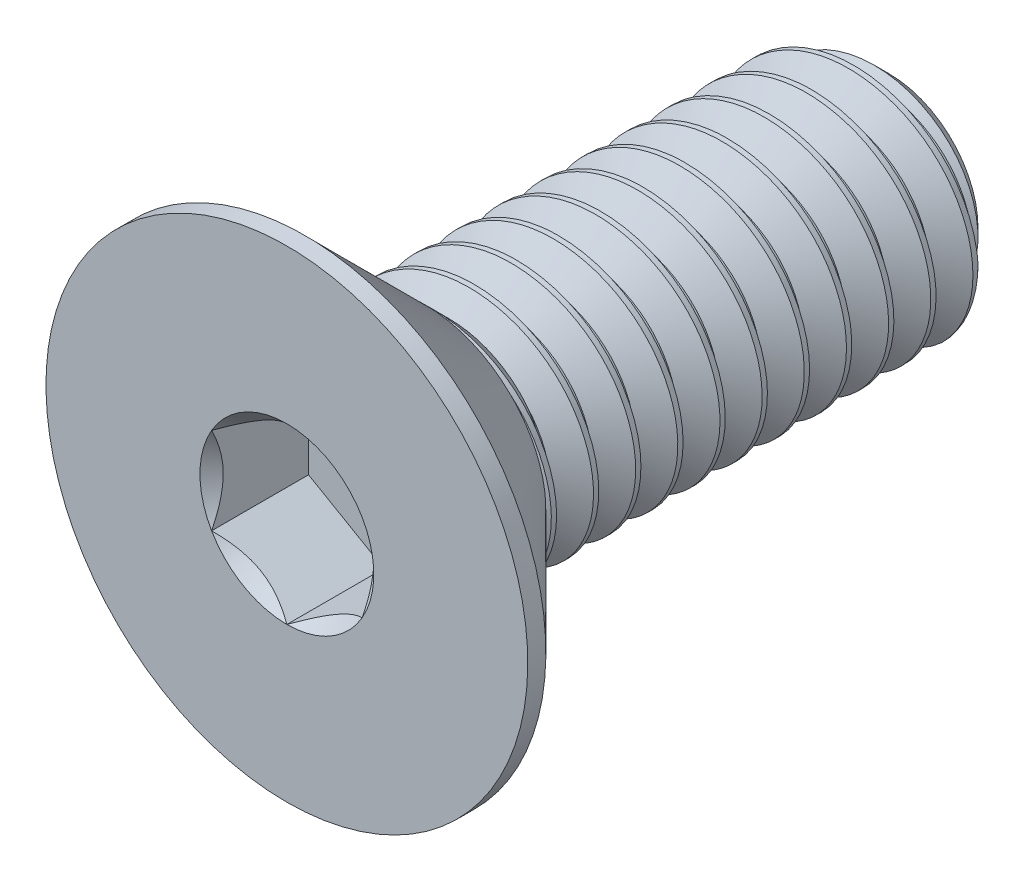
SolidWorks part; units mm, degrees
ref_plane "Front" through (0, 0, 0) normal (0, 0, 1) x (1, 0, 0)
ref_plane "Top" through (0, 0, 0) normal (0, 1, 0) x (1, 0, 0)
ref_plane "Right" through (0, 0, 0) normal (1, 0, 0) x (0, 0, -1)
sketch "Sketch1" plane through (0, 0, 0) normal (1, 0, 0) x (0, 0, -1)
  line L0 (0, 4) -> (0.3, 4) construction
  line L1 (0.3, 4) -> (2.3, 2) construction
  line L2 (0, 2) -> (10, 2)
  line L3 (10, 2) -> (10, 0)
  line L4 (10, 0) -> (0, 0)
  line L5 (0, 0) -> (0, 4) construction
  line L6 (0, 4) -> (0, -4) construction
  line L7 (10, 2) -> (10, -2) construction
  line L8 (0, -4) -> (0.3, -4) construction
  line L9 (0.3, -4) -> (2.3, -2) construction
  line L11 (0, 2) -> (0, 0)
  line L12 (2.3, 2) -> (2.3, 0) construction
  dimension "Head Ht" = 2.3
  dimension "Head Dia" = 8
  dimension "Dia" = 4
  dimension "Lg" = 10
  dimension "Head Angle" = 90
revolve "Revolve1" add sketch "Sketch1" angle 360 mid plane about L4
sketch "Sketch3" plane through (0, 0, -10) normal (0, 0, -1) x (-1, 0, 0)
  circle A0 centre (0, 0) radius 2
curve "Helix/Spiral1" pitch 0.7 height 10 radius 2 centre (0, 0, -10) axis (0, 0, 1) start towards (0, 1, 0)
sketch "Sketch2" plane through (0, 0, 0) normal (1, 0, 0) x (0, 0, -1)
  line L0 (10, 2) -> (10.6125, 2)
  line L1 (10.6125, 2) -> (10.35, 1.5453)
  line L2 (10.35, 1.5453) -> (10.2625, 1.5453)
  line L3 (10.2625, 1.5453) -> (10, 2)
  line L4 (10.1312, 1.7727) -> (10.4812, 1.7727) construction
  dimension "D1" = 60
  dimension "D2" = 0.0875
  dimension "D3" = 0.35
chamfer "Chamfer1" distance 0.525 angle 45 1 edges at (0, 2, -10)
sweep "Cut-Sweep1" cut profiles "Sketch2" path "Helix/Spiral1" align with end faces yes
sketch "Sketch7" plane through (0, 0, 0) normal (1, 0, 0) x (0, 0, -1)
  line L0 (0, 4) -> (0.3, 4) construction
  line L1 (0.3, 4) -> (2.3, 2) construction
  line L2 (0, 4) -> (0.3, 4)
  line L3 (0.3, 4) -> (2.3, 2)
  line L4 (2.3, 2) -> (2.3, 0) construction
  line L5 (2.3, 2) -> (2.3, 0)
  line L7 (0, 0) -> (0, 4) construction
  line L8 (0, 0) -> (0, 4)
  line L9 (0, 0) -> (2.3, 0)
  line L10 (4.4, 0) -> (-4.4, 0) construction
revolve "Revolve2" add sketch "Sketch7" angle 360 mid plane about L9
ref_plane "Plane1" through (0, 0, -2.3) normal (0, 0, 1) x (1, 0, 0)
sketch "Sketch8" plane through (0, 0, -2.3) normal (0, 0, 1) x (1, 0, 0)
  circle A0 centre (0, 0) radius 2
extrude "Boss-Extrude1" add sketch "Sketch8" against normal through all draft 45
sketch "Sketch5" plane through (0, 0, 0) normal (0, 0, 1) x (1, 0, 0)
  line L1 (1.25, -0.7217) -> (1.25, 0.7217)
  line L2 (1.25, 0.7217) -> (0, 1.4434)
  line L3 (0, 1.4434) -> (-1.25, 0.7217)
  line L4 (-1.25, 0.7217) -> (-1.25, -0.7217)
  line L5 (-1.25, -0.7217) -> (0, -1.4434)
  line L6 (0, -1.4434) -> (1.25, -0.7217)
  circle A0 centre (0, 0) radius 1.25 construction
  dimension "Hex" = 2.5
extrude "Cut-Extrude2" cut sketch "Sketch5" against normal blind 1.61
sketch "Sketch6" plane through (0, 0, 0) normal (0, 0, 1) x (1, 0, 0)
  circle A0 centre (0, 0) radius 1.4434
extrude "Cut-Extrude3" cut sketch "Sketch6" against normal blind 1.61 draft 45
sketch "Sketch9" [suppressed] plane through (0, 0, -1.5) normal (0, 0, 1) x (1, 0, 0)
  circle A1 centre (0, 0) radius 1.25
  circle A2 centre (0, 0) radius 1.25
  point P0 (0, 1.25)
  dimension "D1" = 0
extrude "Boss-Extrude2" [suppressed] add sketch "Sketch9" against normal offset from surface (3.5 mm away) 26 up to face at (0, 1.475, -10)
fillet "Fillet1" [suppressed] radius 0.4
sketch "Sketch10" plane through (0, 0, 0) normal (1, 0, 0) x (0, 0, -1)
  line L0 (10, 2) -> (10, -2) construction
  point P0 (8.95, -2)
  dimension "D1" = 1.05
equation "\"D3@Helix/Spiral1\" = \"Lg@Sketch1\""
equation "\"D2@Sketch2\" = \"D4@Helix/Spiral1\" * .125"
equation "\"D3@Sketch2\" = \"D4@Helix/Spiral1\" * .5"
equation "\"D1@Chamfer1\" = \"D4@Helix/Spiral1\" * .75"
equation "\"D1@Cut-Extrude2\" = \"Head Ht@Sketch1\" * .7"
equation "\"D1@Sketch10\" = \"D4@Helix/Spiral1\" * 1.5"
equation "\"D1@Cut-Extrude3\" = \"D1@Cut-Extrude2\""
equation "\"D1@Fillet1\" = \"Dia@Sketch1\" * .1"
